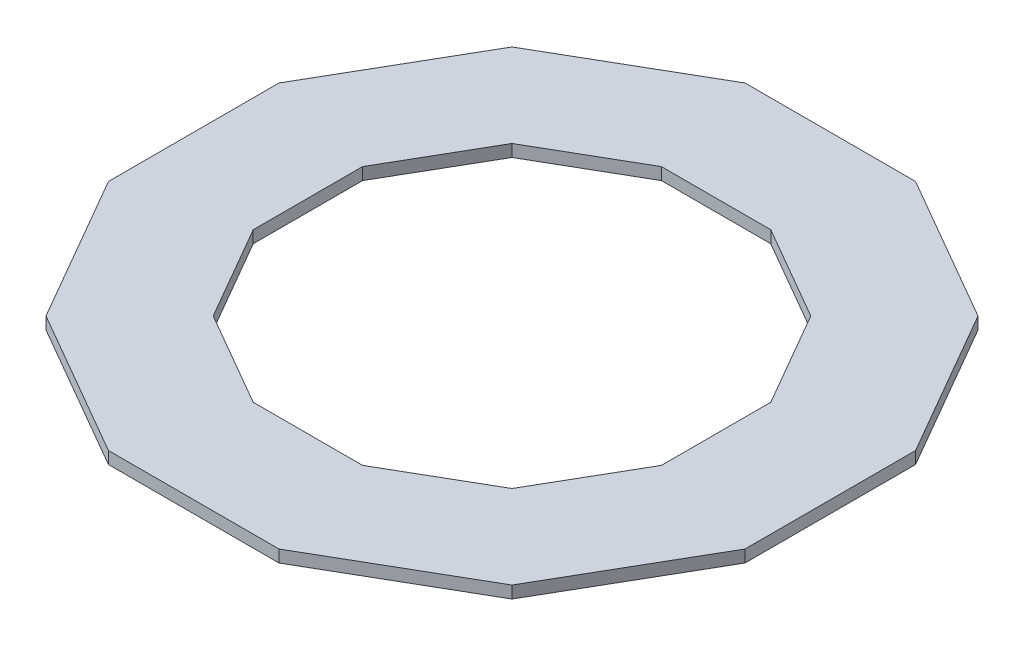
SolidWorks part; units mm, degrees
ref_plane "Front Plane" through (0, 0, 0) normal (0, 0, 1) x (1, 0, 0)
ref_plane "Top Plane" through (0, 0, 0) normal (0, 1, 0) x (1, 0, 0)
ref_plane "Right Plane" through (0, 0, 0) normal (1, 0, 0) x (0, 0, -1)
sketch "Sketch1" plane through (0, 0, 0) normal (0, 1, 0) x (1, 0, 0)
  line L0 (19.722, 73.6035) -> (-19.722, 73.6035)
  line L1 (-19.722, 73.6035) -> (-53.8815, 53.8815)
  line L2 (-53.8815, 53.8815) -> (-73.6035, 19.722)
  line L3 (-73.6035, 19.722) -> (-73.6035, -19.722)
  line L4 (-73.6035, -19.722) -> (-53.8815, -53.8815)
  line L5 (-53.8815, -53.8815) -> (-19.722, -73.6035)
  line L6 (-19.722, -73.6035) -> (19.722, -73.6035)
  line L7 (19.722, -73.6035) -> (53.8815, -53.8815)
  line L8 (53.8815, -53.8815) -> (73.6035, -19.722)
  line L9 (73.6035, -19.722) -> (73.6035, 19.722)
  line L10 (73.6035, 19.722) -> (53.8815, 53.8815)
  line L11 (53.8815, 53.8815) -> (19.722, 73.6035)
  circle A0 centre (0, 0) radius 76.2
  dimension "D1" = 152.4
extrude "Boss-Extrude1" add sketch "Sketch1" against normal blind 2.921 contours L10 L11 L0 L1 L2 L3 L4 L5 L6 L7 L8 L9 region at (0, 0, 0)
sketch "Sketch3" plane through (0, 0, 0) normal (0, 1, 0) x (1, 0, 0)
  line L12 (-35.921, 35.921) -> (-13.148, 49.069)
  line L13 (-13.148, 49.069) -> (13.148, 49.069)
  line L14 (13.148, 49.069) -> (35.921, 35.921)
  line L15 (35.921, 35.921) -> (49.069, 13.148)
  line L16 (49.069, 13.148) -> (49.069, -13.148)
  line L17 (49.069, -13.148) -> (35.921, -35.921)
  line L18 (35.921, -35.921) -> (13.148, -49.069)
  line L19 (13.148, -49.069) -> (-13.148, -49.069)
  line L20 (-13.148, -49.069) -> (-35.921, -35.921)
  line L21 (-35.921, -35.921) -> (-49.069, -13.148)
  line L22 (-49.069, -13.148) -> (-49.069, 13.148)
  line L23 (-49.069, 13.148) -> (-35.921, 35.921)
  line L24 (-53.8815, 53.8815) -> (-73.6035, 19.722) construction
  line L25 (-19.722, 73.6035) -> (-53.8815, 53.8815) construction
  line L26 (19.722, 73.6035) -> (-19.722, 73.6035) construction
  line L27 (53.8815, 53.8815) -> (19.722, 73.6035) construction
  line L28 (73.6035, 19.722) -> (53.8815, 53.8815) construction
  line L29 (73.6035, -19.722) -> (73.6035, 19.722) construction
  line L30 (53.8815, -53.8815) -> (73.6035, -19.722) construction
  line L31 (19.722, -73.6035) -> (53.8815, -53.8815) construction
  line L32 (-19.722, -73.6035) -> (19.722, -73.6035) construction
  line L33 (-53.8815, -53.8815) -> (-19.722, -73.6035) construction
  line L34 (-73.6035, -19.722) -> (-53.8815, -53.8815) construction
  line L35 (-73.6035, 19.722) -> (-73.6035, -19.722) construction
  line L36 (-19.722, 73.6035) -> (19.722, -73.6035) construction
  line L37 (19.722, 73.6035) -> (-19.722, -73.6035) construction
  circle A0 centre (0, 0) radius 50.8
  dimension "D1" = 101.6
extrude "Cut-Extrude1" cut sketch "Sketch3" against normal through all contours L23 L22 L21 L20 L19 L18 L17 L16 L15 L14 L13 L12 region at (0, 0, 0)
sketch "Sketch4" plane through (0, 0, 0) normal (0, 1, 0) x (1, 0, 0)
  line L24 (76.5245, 20.5047) -> (56.0199, 56.0199)
  line L25 (56.0199, 56.0199) -> (20.5047, 76.5245)
  line L26 (20.5047, 76.5245) -> (-20.5047, 76.5245)
  line L27 (-20.5047, 76.5245) -> (-56.0199, 56.0199)
  line L28 (-56.0199, 56.0199) -> (-76.5245, 20.5047)
  line L29 (-76.5245, 20.5047) -> (-76.5245, -20.5047)
  line L30 (-76.5245, -20.5047) -> (-56.0199, -56.0199)
  line L31 (-56.0199, -56.0199) -> (-20.5047, -76.5245)
  line L32 (-20.5047, -76.5245) -> (20.5047, -76.5245)
  line L33 (20.5047, -76.5245) -> (56.0199, -56.0199)
  line L34 (56.0199, -56.0199) -> (76.5245, -20.5047)
  line L35 (76.5245, -20.5047) -> (76.5245, 20.5047)
  line L36 (76.5245, 20.5047) -> (56.0199, 56.0199)
  line L37 (56.0199, 56.0199) -> (20.5047, 76.5245)
  line L38 (20.5047, 76.5245) -> (-20.5047, 76.5245)
  line L39 (-20.5047, 76.5245) -> (-56.0199, 56.0199)
  line L40 (-56.0199, 56.0199) -> (-76.5245, 20.5047)
  line L41 (-76.5245, 20.5047) -> (-76.5245, -20.5047)
  line L42 (-76.5245, -20.5047) -> (-56.0199, -56.0199)
  line L43 (-56.0199, -56.0199) -> (-20.5047, -76.5245)
  line L44 (-20.5047, -76.5245) -> (20.5047, -76.5245)
  line L45 (20.5047, -76.5245) -> (56.0199, -56.0199)
  line L46 (56.0199, -56.0199) -> (76.5245, -20.5047)
  line L47 (76.5245, -20.5047) -> (76.5245, 20.5047)
  line L60 (73.6035, 19.722) -> (53.8815, 53.8815)
  line L61 (53.8815, 53.8815) -> (19.722, 73.6035)
  line L62 (19.722, 73.6035) -> (-19.722, 73.6035)
  line L63 (-19.722, 73.6035) -> (-53.8815, 53.8815)
  line L64 (-53.8815, 53.8815) -> (-73.6035, 19.722)
  line L65 (-73.6035, 19.722) -> (-73.6035, -19.722)
  line L66 (-73.6035, -19.722) -> (-53.8815, -53.8815)
  line L67 (-53.8815, -53.8815) -> (-19.722, -73.6035)
  line L68 (-19.722, -73.6035) -> (19.722, -73.6035)
  line L69 (19.722, -73.6035) -> (53.8815, -53.8815)
  line L70 (53.8815, -53.8815) -> (73.6035, -19.722)
  line L71 (73.6035, -19.722) -> (73.6035, 19.722)
  line L72 (73.6035, 19.722) -> (53.8815, 53.8815)
  line L73 (53.8815, 53.8815) -> (19.722, 73.6035)
  line L74 (19.722, 73.6035) -> (-19.722, 73.6035)
  line L75 (-19.722, 73.6035) -> (-53.8815, 53.8815)
  line L76 (-53.8815, 53.8815) -> (-73.6035, 19.722)
  line L77 (-73.6035, 19.722) -> (-73.6035, -19.722)
  line L78 (-73.6035, -19.722) -> (-53.8815, -53.8815)
  line L79 (-53.8815, -53.8815) -> (-19.722, -73.6035)
  line L80 (-19.722, -73.6035) -> (19.722, -73.6035)
  line L81 (19.722, -73.6035) -> (53.8815, -53.8815)
  line L82 (53.8815, -53.8815) -> (73.6035, -19.722)
  line L83 (73.6035, -19.722) -> (73.6035, 19.722)
  dimension "D1" = 2.921
  dimension "D2" = 0
extrude "Boss-Extrude2" add sketch "Sketch4" against normal up to surface (2.921 mm away) up to face at (0, -2.921, 0)
